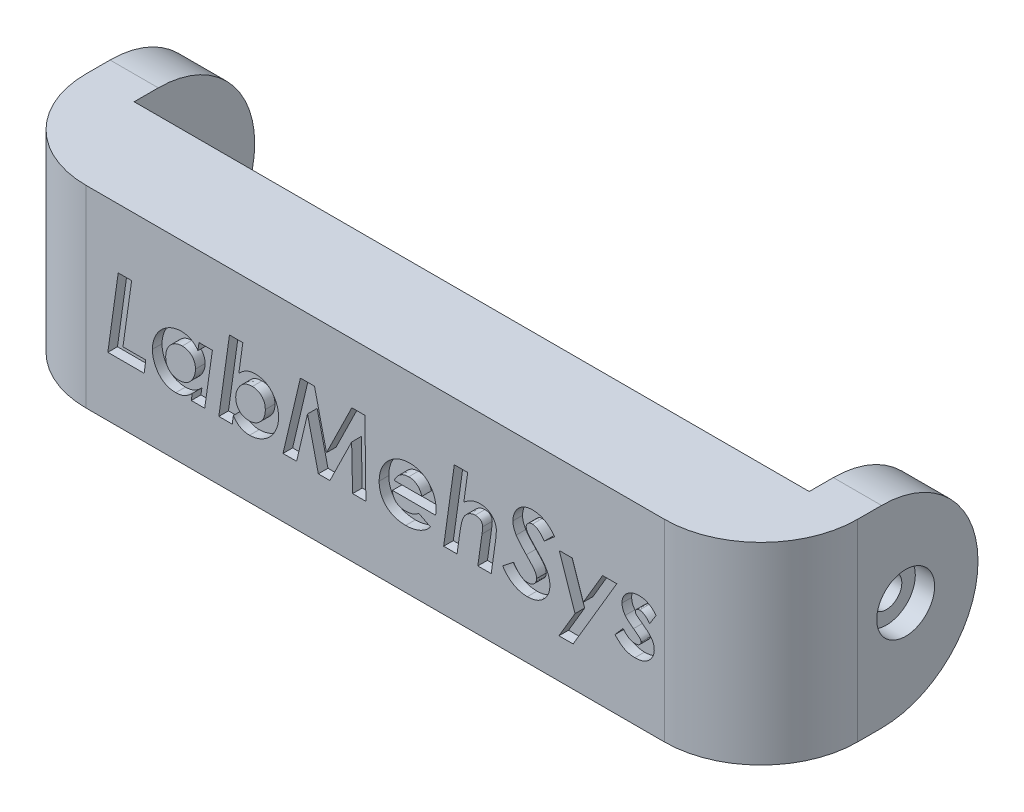
SolidWorks part; units mm, degrees
ref_plane "Front Plane" through (0, 0, 0) normal (0, 0, 1) x (1, 0, 0)
ref_plane "Top Plane" through (0, 0, 0) normal (0, 1, 0) x (1, 0, 0)
ref_plane "Right Plane" through (0, 0, 0) normal (1, 0, 0) x (0, 0, -1)
sketch "Sketch1" plane through (0, 0, 0) normal (0, 1, 0) x (1, 0, 0)
  line L1 (-34.0248, 5.3096) -> (35.9752, 5.3096)
  line L2 (-34.0248, 5.3096) -> (-34.0248, -4.6904)
  line L3 (-34.0248, -4.6904) -> (35.9752, -4.6904)
  line L4 (35.9752, 5.3096) -> (35.9752, -4.6904)
  line L5 (-34.0248, -4.6904) -> (-39.0248, -4.6904)
  line L6 (-34.0248, -4.6904) -> (-34.0248, 17.8096)
  line L7 (-34.0248, 17.8096) -> (-39.0248, 17.8096)
  line L8 (-39.0248, -4.6904) -> (-39.0248, 17.8096)
  line L9 (35.9752, -4.6904) -> (40.9752, -4.6904)
  line L10 (35.9752, -4.6904) -> (35.9752, 17.8096)
  line L11 (35.9752, 17.8096) -> (40.9752, 17.8096)
  line L12 (40.9752, -4.6904) -> (40.9752, 17.8096)
  dimension "D1" = 70
  dimension "D2" = 10
  dimension "D3" = 5
  dimension "D4" = 5
  dimension "D5" = 22.5
  dimension "D6" = 22.5
extrude "Boss-Extrude1" add sketch "Sketch1" along normal blind 20 contours L8 L5 L2 L6 L7 | L4 L1 L2 L3 | L9 L12 L11 L10 L4 region at (0.9752, 0, -0.3096) region at (-36.5248, 0, -6.5596) region at (38.4752, 0, -6.5596)
fillet "Fillet1" radius 10 2 edges at (40.9752, 10, 4.6904) (-39.0248, 10, 4.6904)
fillet "Fillet2" radius 10 4 edges at (-36.5248, 0, -17.8096) (38.4752, 0, -17.8096) (38.4752, 20, -17.8096) (-36.5248, 20, -17.8096)
sketch "Sketch4" plane through (40.9752, 0, 0) normal (1, 0, 0) x (0, 0, -1)
  line L0 (5.3096, 20) -> (7.8096, 20) construction
  line L1 (15.3096, 15) -> (15.3096, 5) construction
  circle A0 centre (10.3096, 10) radius 1.6
  dimension "D3" = 3.2
  dimension "D1" = 10
  dimension "D2" = 5
extrude "Cut-Extrude2" cut sketch "Sketch4" against normal blind 94
sketch "Sketch5" plane through (-39.0248, 0, 0) normal (-1, 0, 0) x (0, 0, 1)
  circle A0 centre (-10.3096, 10) radius 3
  dimension "D1" = 6
extrude "Cut-Extrude3" cut sketch "Sketch5" against normal blind 2
sketch "Sketch6" plane through (40.9752, 0, 0) normal (1, 0, 0) x (0, 0, -1)
  circle A0 centre (10.3096, 10) radius 3
  dimension "D1" = 6
extrude "Cut-Extrude4" cut sketch "Sketch6" against normal blind 2
sketch "Sketch7" plane through (0, 0, 4.6904) normal (0, 0, 1) x (1, 0, 0)
  text T0 "<b><i>LabMehSys</i></b>" font "Century Gothic" height in points 29
extrude "Cut-Extrude5" cut sketch "Sketch7" against normal blind 1
